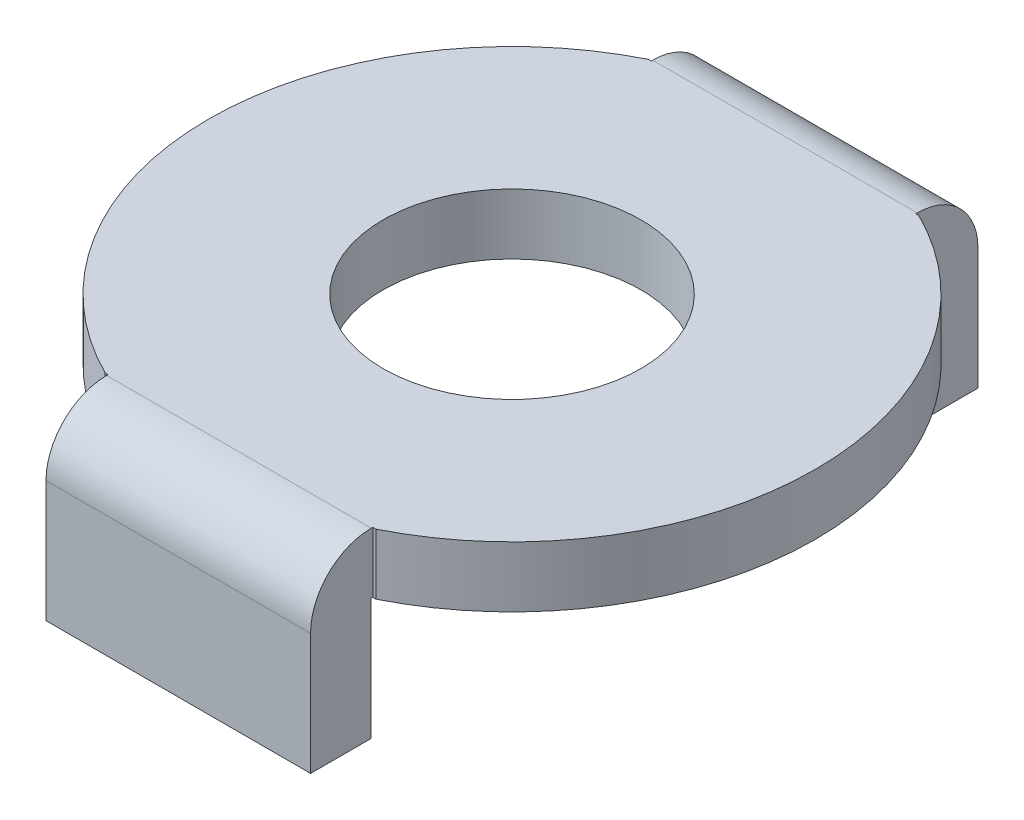
SolidWorks part; units mm, degrees
ref_plane "前视基准面" through (0, 0, 0) normal (0, 0, 1) x (1, 0, 0)
ref_plane "上视基准面" through (0, 0, 0) normal (0, 1, 0) x (1, 0, 0)
ref_plane "右视基准面" through (0, 0, 0) normal (1, 0, 0) x (0, 0, -1)
ref_plane "基准面1" through (0, 0, 0) normal (1, 0, 0) x (0, 0, -1)
sketch "草图1" plane through (0, 0, 0) normal (1, 0, 0) x (0, 0, -1)
  line L0 (-11, 0) -> (-11, -4)
  line L1 (-11, -4) -> (-9, -4)
  line L2 (-9, -4) -> (-9, 0)
  line L3 (-9, 0) -> (9, 0)
  line L4 (9, 0) -> (9, -4)
  line L5 (9, -4) -> (11, -4)
  line L6 (11, -4) -> (11, 0)
  line L7 (9, 2) -> (-9, 2)
  arc A0 (11, 0) -> (9, 2) centre (9, 0) ccw
  arc A1 (-9, 2) -> (-11, 0) centre (-9, 0) ccw
extrude "凸台-拉伸1" add sketch "草图1" against normal blind 4.3603 and the other way blind 4.3603
ref_plane "基准面2" through (0, 0, 0) normal (0, 1, 0) x (1, 0, 0)
sketch "草图2" plane through (0, 0, 0) normal (0, 1, 0) x (1, 0, 0)
  line L0 (-4.4607, -8.95) -> (4.4607, -8.95)
  line L1 (4.4607, 8.95) -> (-4.4607, 8.95)
  arc A0 (-4.4607, 8.95) -> (-4.4607, -8.95) centre (0, 0) ccw
  arc A1 (4.4607, -8.95) -> (4.4607, 8.95) centre (0, 0) ccw
extrude "凸台-拉伸2" add sketch "草图2" along normal blind 2
sketch "草图3" plane through (0, 0, 0) normal (0, 1, 0) x (1, 0, 0)
  circle A0 centre (0, 0) radius 4.25
extrude "切除-拉伸1" cut sketch "草图3" along normal blind 2
ref_plane "基准面3" through (0, 0, 0) normal (1, 0, 0) x (0, 0, -1)
ref_plane "基准面4" through (0, 2, 0) normal (0, 1, 0) x (1, 0, 0)
ref_plane "to_s XY" through (0, 0, 0) normal (1, 0, 0) x (0, 0, -1)
ref_plane "to_s XZ" through (0, 0, 0) normal (0, -1, 0) x (-1, 0, 0)
ref_plane "to_s YZ" through (0, 0, 0) normal (0, 0, -1) x (-1, 0, 0)
ref_axis "to_s X" through (0, 0, 80.9) along (0, 0, -1)
ref_axis "to_s Y" through (0, -50, 0) along (0, 1, 0)
ref_axis "to_s Z" through (80.9, 0, 0) along (-1, 0, 0)
sketch3d "to_s"
  point P0 (0, 0, 0)
ref_plane "to_nut XY" through (0, 2, 0) normal (0, -1, 0) x (-1, 0, 0)
ref_plane "to_nut XZ" through (0, 0, 0) normal (0, 0, -1) x (-1, 0, 0)
ref_plane "to_nut YZ" through (0, 0, 0) normal (1, 0, 0) x (0, 0, -1)
ref_axis "to_nut X" through (-80.9, 2, 0) along (1, 0, 0)
ref_axis "to_nut Y" through (0, 2, -50) along (0, 0, 1)
ref_axis "to_nut Z" through (0, -50, 0) along (0, 1, 0)
sketch3d "to_nut"
  point P0 (0, 2, 0)
equation "\"零件重量\"= \"SW-质量\""
